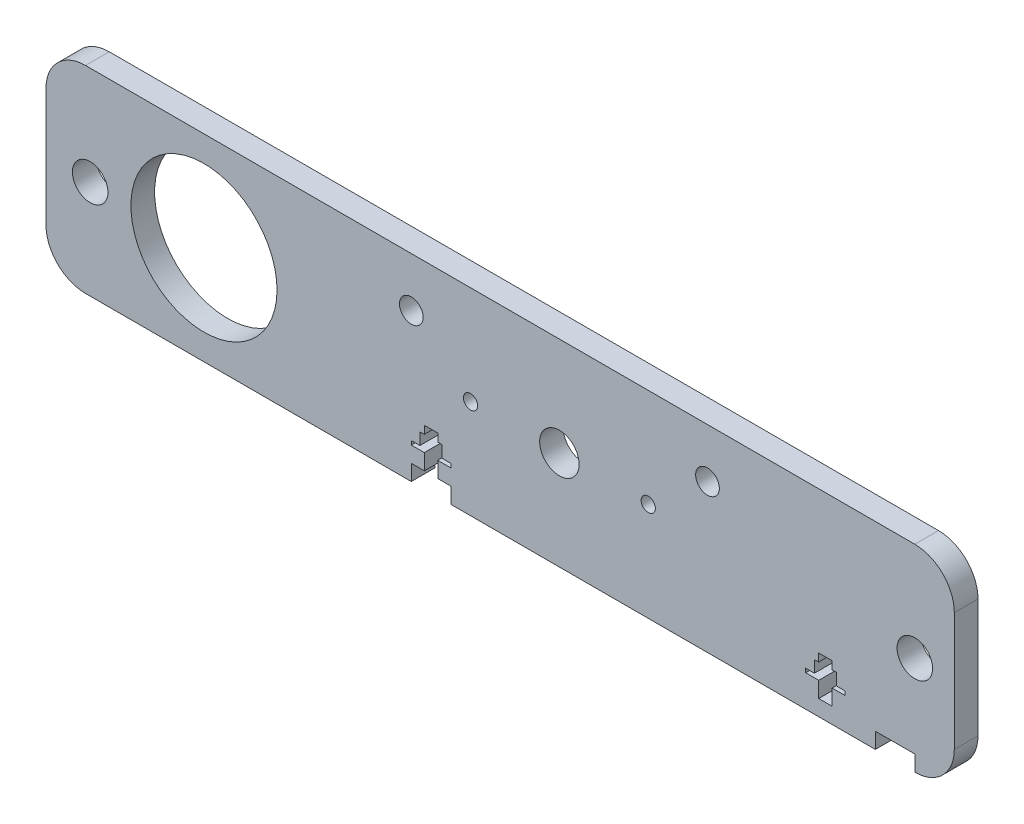
SolidWorks part; units mm, degrees
material "Balsa"
ref_plane "Plano frontal" through (0, 0, 0) normal (0, 0, 1) x (1, 0, 0)
ref_plane "Plano superior" through (0, 0, 0) normal (0, 1, 0) x (1, 0, 0)
ref_plane "Plano direito" through (0, 0, 0) normal (1, 0, 0) x (0, 0, -1)
sketch "Esboço1" plane through (0, 0, 0) normal (0, 0, 1) x (1, 0, 0)
  line L0 (105, -25) -> (105, -21)
  line L1 (-105, -25) -> (-22.5, -25)
  line L2 (-115, -15) -> (-115, 15)
  line L3 (-105, 25) -> (105, 25)
  line L4 (115, -15) -> (115, 15)
  line L5 (-115, -25) -> (115, 25) construction
  line L6 (-115, 25) -> (115, -25) construction
  line L7 (-75, 18.5) -> (-75, 25) construction
  line L8 (15, 25) -> (15, 0) construction
  line L9 (-99.31, 0) -> (-99.31, 1.5)
  line L10 (-22.5, 12.5) -> (52.5, 12.5) construction
  line L11 (-7.5, 0) -> (37.5, 0) construction
  line L12 (105, -21) -> (84.07, -21)
  line L13 (95, -21) -> (95, -25)
  line L14 (-22.5, -25) -> (-22.5, -21)
  line L15 (-22.5, -21) -> (-19.2, -21)
  line L16 (-12.5, -21) -> (-12.5, -25)
  line L17 (-12.5, -25) -> (95, -25)
  line L18 (-17.5, -25) -> (-17.5, -13.0244) construction
  line L19 (-19.2, -21) -> (-19.2, -17)
  line L20 (-19.2, -17) -> (-22.5, -17)
  line L21 (-20.3, -16) -> (-20.3, -13)
  line L22 (-20.3, -13) -> (-19.2, -13)
  line L23 (-22.5, -25) -> (-12.5, -25) construction
  line L24 (-19.2, -13) -> (-19.2, -11)
  line L25 (-19.2, -11) -> (-15.8, -11)
  line L26 (-20.3, -16) -> (-22.5, -16)
  line L27 (-22.5, -16) -> (-22.5, -17)
  line L28 (-12.5, -16) -> (-12.5, -17)
  line L29 (-14.7, -16) -> (-12.5, -16)
  line L30 (-15.8, -13) -> (-15.8, -11)
  line L31 (-14.7, -13) -> (-15.8, -13)
  line L32 (-14.7, -16) -> (-14.7, -13)
  line L33 (-15.8, -17) -> (-12.5, -17)
  line L34 (-15.8, -21) -> (-15.8, -17)
  line L35 (-12.5, -21) -> (-15.8, -21)
  line L36 (87.37, -16) -> (87.37, -17)
  line L37 (77.37, -16) -> (77.37, -17)
  line L38 (84.07, -17) -> (87.37, -17)
  line L39 (80.67, -17) -> (77.37, -17)
  line L40 (84.07, -13) -> (84.07, -11)
  line L41 (85.17, -13) -> (84.07, -13)
  line L42 (80.67, -13) -> (80.67, -11)
  line L43 (80.67, -11) -> (84.07, -11)
  line L44 (80.67, -21) -> (80.67, -17)
  line L45 (82.37, -25) -> (82.37, -15.5244) construction
  line L46 (79.57, -16) -> (79.57, -13)
  line L47 (84.07, -21) -> (84.07, -17)
  line L48 (85.17, -16) -> (87.37, -16)
  line L49 (79.57, -16) -> (77.37, -16)
  line L50 (79.57, -13) -> (80.67, -13)
  line L51 (85.17, -16) -> (85.17, -13)
  line L52 (80.67, -21) -> (95, -21)
  circle A0 centre (-75, 0) radius 18.5
  circle A1 centre (105, 0) radius 4.5
  arc A2 (105, -25) -> (115, -15) centre (105, -15) ccw
  arc A3 (105, 25) -> (115, 15) centre (105, 15) cw
  arc A4 (-115, 15) -> (-105, 25) centre (-105, 15) cw
  arc A5 (-105, -25) -> (-115, -15) centre (-105, -15) cw
  circle A6 centre (15, 0) radius 5
  circle A7 centre (-103.81, 0) radius 4.5
  circle A8 centre (-7.5, 0) radius 1.8
  circle A9 centre (37.5, 0) radius 1.8
  circle A10 centre (-22.5, 12.5) radius 3
  circle A11 centre (52.5, 12.5) radius 3
  point P0 (0, 0)
  point P5 (0, 0)
  point P34 (15, 12.5)
  point P35 (15, 0)
  point P42 (15, 12.5)
  point P60 (-17.5, -25)
  point P67 (-17.5, -11)
  point P84 (94.8463, -8.5)
  point P88 (0, 0)
  point P89 (98.5993, 0)
  point P90 (0, 0)
  point P91 (0, 0)
  point P92 (0, 0)
  point P94 (0, 0)
  point P95 (0, 0)
  point P96 (0, 0)
  dimension "D3" = 37
  dimension "D5" = 9
  dimension "D6" = 10
  dimension "D9" = 28.81
  dimension "D10" = 75
  dimension "D11" = 6
  dimension "D12" = 3.6
  dimension "D14" = 10
  dimension "D1" = 230
  dimension "D2" = 50
  dimension "D4" = 180
  dimension "D7" = 4
  dimension "D8" = 10
  dimension "D13" = 45
  dimension "D15" = 10
  dimension "D16" = 10
  dimension "D17" = 4
  dimension "D18" = 4
  dimension "D19" = 4
  dimension "D20" = 5.6
  dimension "D21" = 3.4
  dimension "D22" = 2
  dimension "D23" = 1
  dimension "D24" = 10
  dimension "D25" = 4
  dimension "D26" = 3.4
  dimension "D27" = 5.6
  dimension "D28" = 2
  dimension "D29" = 4
  dimension "D30" = 1
  dimension "D31" = 10
  dimension "D32" = 10
  dimension "D33" = 15
extrude "Ressalto-extrusão1" add sketch "Esboço1" along normal blind 6 contours A5 L1 A2 L4 A3 L3 A4 L2 A11 A10 A9 A8 A6 A1 A0 A7 region at (7.2731, 0.2662, 0)
